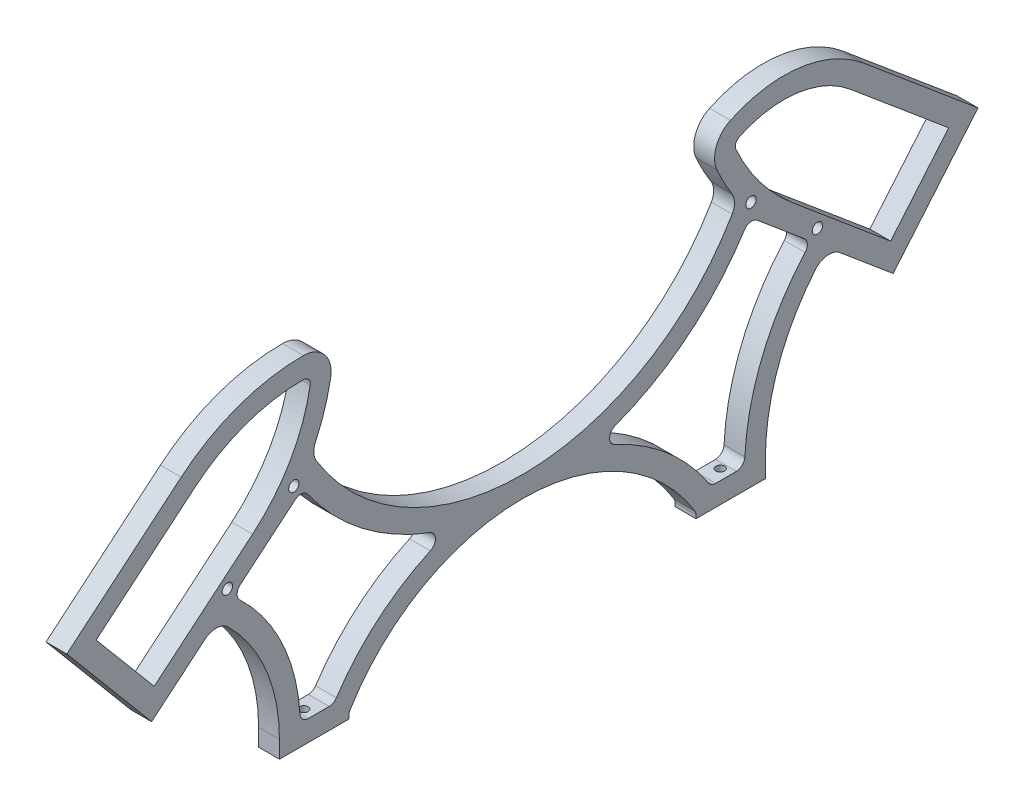
SolidWorks part; units mm, degrees
material "1060 Alloy"
ref_plane "Front Plane" through (0, 0, 0) normal (0, 0, 1) x (1, 0, 0)
ref_plane "Top Plane" through (0, 0, 0) normal (0, 1, 0) x (1, 0, 0)
ref_plane "Right Plane" through (0, 0, 0) normal (1, 0, 0) x (0, 0, -1)
sketch "Sketch1" plane through (0, 0, 0) normal (1, 0, 0) x (0, 0, -1)
  line L0 (0, 0) -> (0, 5)
  line L1 (-60.4789, 57.5279) -> (-34.1246, 26.1201) construction
  line L2 (-60.4789, 57.5279) -> (0.8047, 108.9509) construction
  line L3 (-34.1246, 26.1201) -> (27.1589, 77.5431) construction
  line L4 (-57.0184, 56.5154) -> (-36.4492, 32.0019) construction
  line L5 (0.8047, 108.9509) -> (27.1589, 77.5431) construction
  line L6 (20, 1) -> (20, 0)
  line L7 (0, 0) -> (20, 0)
  line L8 (-36.4492, 32.0019) -> (-5.8075, 57.7135) construction
  line L9 (-26.3767, 82.2269) -> (-57.0184, 56.5154) construction
  line L10 (153.1942, 52.599) -> (135.4467, 67.4909)
  line L11 (-28.305, 84.525) -> (-61.2449, 56.8851)
  line L12 (6.6426, 64.2441) -> (-13.5041, 47.339)
  line L13 (134.0073, 6) -> (124.3139, 6)
  line L14 (200.4789, 62.5279) -> (174.1246, 31.1201) construction
  line L15 (200.4789, 62.5279) -> (139.1953, 113.9509) construction
  line L16 (174.1246, 31.1201) -> (112.8411, 82.5431) construction
  line L17 (139.1953, 113.9509) -> (112.8411, 82.5431) construction
  line L18 (176.4492, 37.0019) -> (197.0184, 61.5154) construction
  line L19 (197.0184, 61.5154) -> (166.3767, 87.2269) construction
  line L20 (145.8075, 62.7135) -> (176.4492, 37.0019) construction
  line L21 (186.7338, 49.2587) -> (126.9824, 99.3961) construction
  line L22 (-46.7338, 44.2587) -> (13.0176, 94.3961) construction
  line L23 (15.6861, 6) -> (5.991, 6)
  line L24 (161.4981, 45.6312) -> (176.819, 32.7755)
  line L25 (176.819, 32.7755) -> (201.2449, 61.8851)
  line L26 (201.2449, 61.8851) -> (168.305, 89.525)
  line L27 (-61.2449, 56.8851) -> (-36.819, 27.7755)
  line L28 (140, 0) -> (140, 5)
  line L29 (-36.819, 27.7755) -> (-21.4981, 40.6312)
  line L30 (-36.819, 27.7755) -> (-3.8791, 55.4153) construction
  line L31 (147.7358, 65.0116) -> (176.0795, 41.2284)
  line L32 (176.0795, 41.2284) -> (192.792, 61.1456)
  line L33 (192.792, 61.1456) -> (164.4483, 84.9287)
  line L34 (109.9256, 30) -> (27.8477, 30) construction
  line L35 (109.9256, 36) -> (27.8477, 36) construction
  line L36 (135.0961, 75.6176) -> (155.3963, 58.5837) construction
  line L37 (-24.4483, 79.9287) -> (-52.792, 56.1456)
  line L38 (-52.792, 56.1456) -> (-36.0795, 36.2284)
  line L39 (-36.0795, 36.2284) -> (-7.7358, 60.0116)
  line L40 (143.8791, 60.4153) -> (176.819, 32.7755) construction
  line L41 (135.0961, 75.6176) -> (152.13, 95.9178) construction
  line L42 (155.3963, 58.5837) -> (172.4301, 78.8839) construction
  line L43 (140, 0) -> (120, 0)
  line L44 (152.13, 95.9178) -> (172.4301, 78.8839) construction
  line L56 (120, 1) -> (120, 0)
  line L63 (174.6584, 98) -> (-14.1241, 98) construction
  circle A0 centre (-15, 50) radius 1.5
  circle A1 centre (155, 55) radius 1.5
  circle A2 centre (4.1511, 66.0697) radius 1.5
  circle A3 centre (135.8489, 71.0697) radius 1.5
  circle A4 centre (155, 55) radius 3 construction
  circle A5 centre (135.8489, 71.0697) radius 3 construction
  circle A6 centre (-15, 50) radius 3 construction
  circle A7 centre (4.1511, 66.0697) radius 3 construction
  arc A8 (168.305, 89.525) -> (129.9204, 94.4491) centre (145.2761, 62.0802) ccw
  arc A9 (129.9204, 94.4491) -> (126.0591, 83.9267) centre (133.3493, 87.2212) ccw
  arc A10 (126.0591, 83.9267) -> (130.3352, 75.9601) centre (186.5435, 111.2608) ccw
  arc A11 (10.3664, 73.9036) -> (14.7742, 87.9021) centre (-38.8526, 97.0951) ccw
  arc A12 (-5.8075, 57.7135) -> (11.8174, 88.409) centre (-38.8526, 97.0951) ccw construction
  arc A13 (11.8174, 88.409) -> (6.9131, 94.2537) centre (6.8893, 89.2538) ccw construction
  arc A14 (6.9131, 94.2537) -> (-26.3767, 82.2269) centre (6.6685, 42.8452) ccw construction
  arc A15 (166.3767, 87.2269) -> (131.2062, 91.7387) centre (145.2761, 62.0802) ccw construction
  arc A16 (131.2062, 91.7387) -> (128.7929, 85.1621) centre (133.3493, 87.2212) ccw construction
  arc A17 (128.7929, 85.1621) -> (145.8075, 62.7135) centre (186.5435, 111.2608) ccw construction
  arc A18 (14.7742, 87.9021) -> (6.9273, 97.2537) centre (6.8893, 89.2538) ccw
  arc A19 (6.9273, 97.2537) -> (-28.305, 84.525) centre (6.6685, 42.8452) ccw
  arc A20 (164.4483, 84.9287) -> (132.492, 89.0282) centre (145.2761, 62.0802) ccw
  arc A21 (132.492, 89.0282) -> (131.5267, 86.3976) centre (133.3493, 87.2212) ccw
  arc A22 (131.5267, 86.3976) -> (147.7358, 65.0116) centre (186.5435, 111.2608) ccw
  arc A23 (-3.8791, 55.4153) -> (14.7742, 87.9021) centre (-38.8526, 97.0951) ccw construction
  arc A24 (124.3139, 6) -> (90.2116, 32.7337) centre (70, -28.1667) ccw
  arc A25 (49.823, 32.7451) -> (6.6426, 64.2441) centre (70.038, 105.8033) cw
  arc A26 (20, 1) -> (20.2908, 2.0386) centre (22, 1) cw
  arc A27 (-7.7358, 60.0116) -> (8.8605, 88.9159) centre (-38.8526, 97.0951) ccw
  arc A28 (8.8605, 88.9159) -> (6.8988, 91.2538) centre (6.8893, 89.2538) ccw
  arc A29 (6.8988, 91.2538) -> (-24.4483, 79.9287) centre (6.6685, 42.8452) ccw
  arc A30 (126.0591, 83.9267) -> (143.8791, 60.4153) centre (186.5435, 111.2608) ccw construction
  arc A31 (135.4467, 67.4909) -> (90.2116, 32.7337) centre (70.038, 105.8033) cw
  arc A32 (140, 5) -> (154.437, 44.9946) centre (202.6167, 5) cw
  arc A33 (161.4981, 45.6312) -> (154.437, 44.9946) centre (158.2842, 41.801) ccw
  arc A34 (0, 5) -> (-14.7699, 40.3576) centre (-49.7062, 5) ccw
  arc A35 (-21.4981, 40.6312) -> (-14.7699, 40.3576) centre (-18.2842, 36.801) cw
  arc A36 (130.3352, 75.9601) -> (130.4266, 70.7931) centre (126.101, 73.3009) cw
  arc A37 (10.3664, 73.9036) -> (10.6343, 69.1467) centre (14.8894, 71.7724) ccw
  arc A38 (130.4266, 70.7931) -> (10.6343, 69.1467) centre (70.038, 105.8033) cw
  arc A39 (153.1942, 52.599) -> (134.0073, 6) centre (202.6167, 5) ccw
  arc A40 (-13.5041, 47.339) -> (5.991, 6) centre (-49.7062, 5) cw
  arc A41 (49.823, 32.7451) -> (15.6861, 6) centre (70, -28.1667) ccw
  arc A42 (129.9204, 94.4491) -> (126.0591, 83.9267) centre (133.3493, 87.2212) ccw construction
  arc A44 (120, 1) -> (119.7092, 2.0386) centre (118, 1) ccw
  arc A45 (119.7092, 2.0386) -> (20.2908, 2.0386) centre (70, -28.1667) ccw
  dimension "D1" = 3
  dimension "D8" = 5
  dimension "D11" = 55
  dimension "D12" = 15
  dimension "D14" = 25
  dimension "D16" = 2
  dimension "D17" = 6
  dimension "D21" = 40
  dimension "D22" = 35
  dimension "D23" = 80
  dimension "D24" = 3
  dimension "D18" = 6
  dimension "D29" = 50
  dimension "D25" = 5
  dimension "D28" = 6
  dimension "D36" = 5
  dimension "D37" = 20
  dimension "D38" = 10
  dimension "D39" = 8
  dimension "D40" = 10
  dimension "D45" = 6
  dimension "D46" = 6
  dimension "D47" = 6
  dimension "D48" = 6
  dimension "D49" = 30
  dimension "D52" = 26.5
  dimension "D53" = 3
  dimension "D56" = 2
  dimension "D4" = 25
  dimension "D6" = 28
  dimension "D7" = 15
  dimension "D9" = 20
  dimension "D10" = 100
  dimension "D13" = 1
  dimension "D15" = 40
  dimension "D19" = 40
  dimension "D20" = 30
  dimension "D26" = 3
  dimension "D27" = 2
  dimension "D30" = 3
  dimension "D31" = 3
  dimension "D32" = 98
  dimension "D33" = 3
  dimension "D34" = 6
  dimension "D35" = 3
  dimension "D41" = 3
  dimension "D42" = 3
  dimension "D43" = 6
  dimension "D44" = 6
  dimension "D50" = 3.5
  dimension "D51" = 26.5
extrude "Boss-Extrude1" add sketch "Sketch1" along normal blind 6
hole_wizard "Tap Drill for M3 Tap1" positions "Sketch3" profile "Sketch2" hole size "M3" standard "ISO"
sketch "Sketch3" plane through (0, 0, 0) normal (0, -1, 0) x (-1, 0, 0)
  line L0 (-6, 20) -> (0, 20) construction
  line L1 (0, 0) -> (0, 20) construction
  line L2 (-6, 120) -> (0, 120) construction
  point P0 (-3, 10)
  point P2 (-3, 130)
  dimension "D1" = 10
  dimension "D2" = 3
  dimension "D3" = 10
sketch "Sketch2" plane through (3, 0, -10) normal (1, 0, 0) x (0, 0, -1)
  line L0 (0, 0) -> (0, 10.7511)
  line L1 (0, 10.7511) -> (1.25, 10)
  line L2 (1.25, 10) -> (1.25, 0)
  line L5 (1.25, 0) -> (0, 0)
  line L10 (0, 10.7511) -> (-1.25, 10) construction
  line L11 (0, -6.35) -> (0, 107.95) construction
  dimension "Hole Dia." = 2.5
  dimension "Hole Depth" = 10
  dimension "Drill Angle" = 118
fillet "Fillet1" radius 2.5 10 edges at (3, 6, -15.6861) (3, 6, -5.991) (3, 47.339, 13.5041) (3, 64.2441, -6.6426) (3, 52.599, -153.1942) (3, 6, -134.0073) (3, 67.4909, -135.4467) (3, 32.7451, -49.823) (3, 6, -124.3139) (3, 32.7337, -90.2116)
equation "\"ˇ35\"=76.24"
